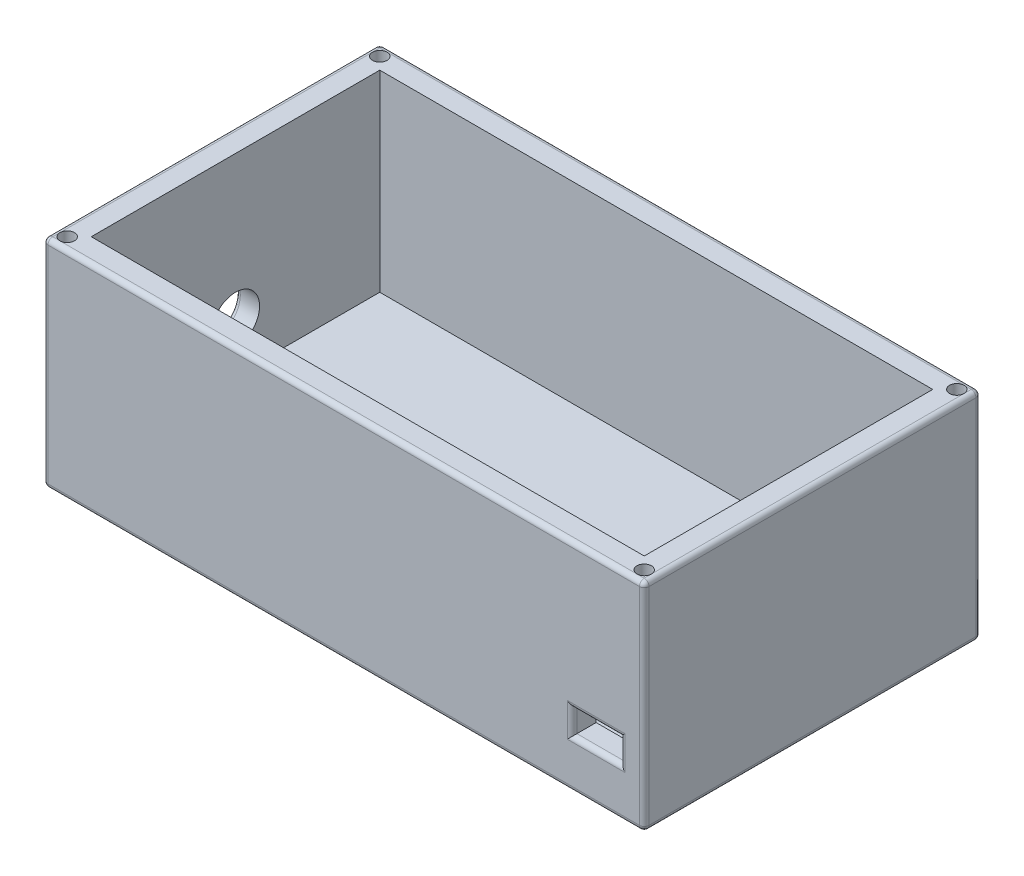
SolidWorks part; units mm, degrees
ref_plane "Front Plane" through (0, 0, 0) normal (0, 0, 1) x (1, 0, 0)
ref_plane "Top Plane" through (0, 0, 0) normal (0, 1, 0) x (1, 0, 0)
ref_plane "Right Plane" through (0, 0, 0) normal (1, 0, 0) x (0, 0, -1)
sketch "Sketch1" plane through (0, 0, 0) normal (0, 1, 0) x (1, 0, 0)
  line L1 (0, 0) -> (125, 0)
  line L2 (0, 0) -> (0, 70)
  line L3 (0, 70) -> (125, 70)
  line L4 (125, 0) -> (125, 70)
extrude "Boss-Extrude1" add sketch "Sketch1" along normal blind 5
sketch "Sketch2" plane through (0, 0, 0) normal (0, -1, 0) x (1, 0, 0)
  line L0 (0, -35) -> (125, -35) construction
  line L1 (0, -70) -> (0, 0) construction
  line L2 (125, 0) -> (125, -70) construction
  line L3 (62.5, -35) -> (115.1516, -35) construction
  line L4 (62.5, -35) -> (62.5, -15.7641) construction
  line L5 (112.7, -35) -> (112.7, -14.6) construction
  circle A0 centre (112.7, -14.6) radius 2.5
  circle A1 centre (112.7, -55.4) radius 2.5
  circle A2 centre (12.3, -14.6) radius 2.5
extrude "Cut-Extrude1" cut sketch "Sketch2" against normal up to next contours A0 | A1 | A2 region at (112.7, 0, -14.6) region at (112.7, 0, -55.4)
sketch "Sketch3" plane through (0, 5, 0) normal (0, 1, 0) x (1, 0, 0)
  line L0 (0, 70) -> (0, 0) construction
  line L1 (0, 0) -> (0, 5) construction
  line L2 (0, 5) -> (5, 5) construction
  line L3 (125, 70) -> (0, 70) construction
  line L4 (5, 5) -> (120, 5)
  line L5 (5, 5) -> (5, 65)
  line L6 (5, 65) -> (120, 65)
  line L7 (120, 5) -> (120, 65)
  line L8 (125, 0) -> (125, 70) construction
  line L10 (0, 0) -> (125, 0)
  line L11 (0, 0) -> (0, 70)
  line L12 (0, 70) -> (125, 70)
  line L13 (125, 0) -> (125, 70)
  dimension "D1" = 5
  dimension "D2" = 5
extrude "Boss-Extrude2" add sketch "Sketch3" along normal blind 40
sketch "Sketch4" plane through (0, 0, 0) normal (-1, 0, 0) x (0, 0, 1)
  line L0 (-35, 0) -> (-35, 5) construction
  line L1 (-70, 0) -> (0, 0) construction
  line L2 (-35, 5) -> (-35, 15) construction
  circle A0 centre (-35, 15) radius 5
extrude "Cut-Extrude2" cut sketch "Sketch4" against normal up to next contours A0
sketch "Sketch6" plane through (0, 0, -70) normal (0, 0, -1) x (-1, 0, 0)
  line L0 (-125, 0) -> (-125, 10) construction
  line L1 (-125, 45) -> (-125, 0) construction
  line L2 (-125, 10) -> (-120, 10) construction
  line L4 (-120, 10) -> (-110, 10)
  line L5 (-120, 10) -> (-120, 15)
  line L6 (-120, 15) -> (-110, 15)
  line L7 (-110, 10) -> (-110, 15)
extrude "Cut-Extrude3" cut sketch "Sketch6" against normal through all both and the other way through all
sketch "Sketch7" plane through (0, 45, 0) normal (0, 1, 0) x (1, 0, 0)
  line L0 (5, 5) -> (0, 0) construction
  line L1 (5, 35) -> (0, 35) construction
  line L2 (5, 65) -> (5, 5) construction
  line L3 (0, 70) -> (0, 0) construction
  line L4 (62.5, 0) -> (62.5, 5) construction
  line L5 (0, 0) -> (125, 0) construction
  line L6 (5, 5) -> (120, 5) construction
  circle A0 centre (2.5, 2.5) radius 1.5
  circle A1 centre (2.5, 67.5) radius 1.5
  circle A2 centre (122.5, 67.5) radius 1.5
  circle A3 centre (122.5, 2.5) radius 1.5
  dimension "D1" = 3
extrude "Cut-Extrude4" cut sketch "Sketch7" against normal blind 20
fillet "Fillet2" radius 1 24 edges at (12.3, 0, -12.1) (112.7, 0, -17.1) (112.7, 0, -57.9) (125, 45, -35) (125, 0, -35) (125, 22.5, -70) (62.5, 45, -70) (62.5, 0, -70) (120, 12.5, -70) (115, 10, -70) (110, 12.5, -70) (115, 15, -70) (0, 22.5, -70) (0, 45, -35) (0, 0, -35) (0, 15, -30) (0, 22.5, 0) (62.5, 45, 0) (125, 22.5, 0) (62.5, 0, 0) (120, 12.5, 0) (115, 15, 0) (110, 12.5, 0) (115, 10, 0)
